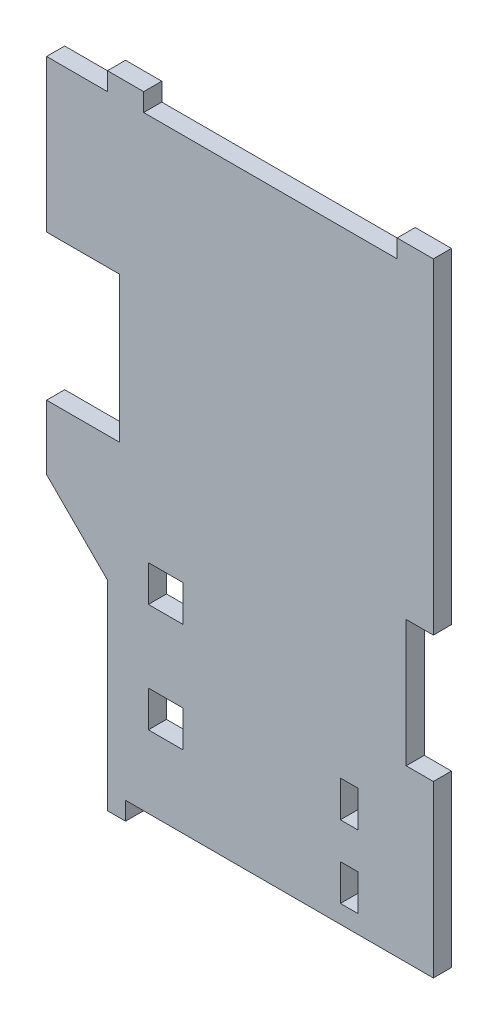
SolidWorks part; units mm, degrees
ref_plane "Plan de face" through (0, 0, 0) normal (0, 0, 1) x (1, 0, 0)
ref_plane "Plan de dessus" through (0, 0, 0) normal (0, 1, 0) x (1, 0, 0)
ref_plane "Plan de droite" through (0, 0, 0) normal (1, 0, 0) x (0, 0, -1)
sketch "Esquisse1" plane through (0, 0, 0) normal (0, 0, 1) x (1, 0, 0)
  line L0 (90, 82) -> (90, 167)
  line L1 (5, 0) -> (90, 0)
  line L2 (0, 0) -> (0, 167)
  line L3 (10, 167) -> (80, 167)
  line L4 (90, 0) -> (90, 47)
  line L5 (90, 82) -> (82.5, 82)
  line L6 (0, 167) -> (0, 172)
  line L7 (0, 172) -> (10, 172)
  line L8 (10, 167) -> (10, 172)
  line L9 (0, 0) -> (0, -5)
  line L10 (90, 167) -> (90, 172)
  line L11 (90, 172) -> (80, 172)
  line L12 (80, 167) -> (80, 172)
  line L13 (0, -5) -> (5, -5)
  line L14 (5, 0) -> (5, -5)
  line L15 (64.3348, 35) -> (64.3348, 25)
  line L16 (90, 47) -> (82.5, 47)
  line L17 (82.5, 82) -> (82.5, 47)
  line L18 (64.3348, 35) -> (69.1423, 35)
  line L19 (64.3348, 25) -> (69.1423, 25)
  line L20 (69.1423, 35) -> (69.1423, 25)
  line L21 (71.3405, 35) -> (66.533, 35) construction
  line L22 (64.3348, 35) -> (64.3348, 25) construction
  line L23 (69.1423, 35) -> (69.1423, 25) construction
  line L24 (18.5374, 30) -> (3.1837, 30) construction
  line L25 (64.3348, 15) -> (69.1423, 15)
  line L26 (64.3348, 15) -> (64.3348, 5)
  line L27 (64.3348, 5) -> (69.1423, 5)
  line L28 (69.1423, 15) -> (69.1423, 5)
  line L29 (11.3034, 30) -> (20.8832, 30)
  line L30 (11.3034, 30) -> (11.3034, 20)
  line L31 (11.3034, 20) -> (20.8832, 20)
  line L32 (20.8832, 30) -> (20.8832, 20)
  line L33 (3.1837, 20) -> (18.5374, 20) construction
  line L36 (21.1471, 30) -> (5.7933, 30) construction
  line L37 (11.3034, 60) -> (20.8832, 60)
  line L38 (11.3034, 60) -> (11.3034, 50)
  line L39 (11.3034, 50) -> (20.8832, 50)
  line L40 (20.8832, 60) -> (20.8832, 50)
  dimension "D1" = 167
  dimension "D2" = 90
  dimension "D3" = 10
  dimension "D4" = 5
  dimension "D5" = 5
  dimension "D6" = 7.5
  dimension "D7" = 35
  dimension "D8" = 82
  dimension "D9" = 10
  dimension "D10" = 10
  dimension "D11" = 10
extrude "Boss.-Extru.1" add sketch "Esquisse1" along normal blind 5
sketch "Esquisse2" plane through (0, 0, 5) normal (0, 0, 1) x (1, 0, 0)
  line L0 (0, 172) -> (0, -5) construction
  line L1 (0, 167) -> (-16.8145, 167)
  line L2 (0, 167) -> (0, 50.1855)
  line L3 (0, 50.1855) -> (-16.8145, 67)
  line L4 (-16.8145, 167) -> (-16.8145, 67)
  line L6 (80, 167) -> (10, 167) construction
  dimension "D1" = 16.8145
  dimension "D2" = 135
  dimension "D3" = 100
extrude "Boss.-Extru.2" add sketch "Esquisse2" against normal blind 5
sketch "Esquisse3" plane through (0, 0, 5) normal (0, 0, 1) x (1, 0, 0)
  line L0 (0, 167) -> (-16.8145, 167) construction
  line L1 (3.3855, 125) -> (-16.8145, 125)
  line L2 (3.3855, 125) -> (3.3855, 84.8)
  line L3 (3.3855, 84.8) -> (-16.8145, 84.8)
  line L4 (-16.8145, 125) -> (-16.8145, 84.8)
  line L5 (-16.8145, 167) -> (-16.8145, 67) construction
  dimension "D1" = 42
  dimension "D2" = 20.2
  dimension "D3" = 40.2
extrude "Enlèv. mat.-Extru.1" cut sketch "Esquisse3" against normal blind 5
